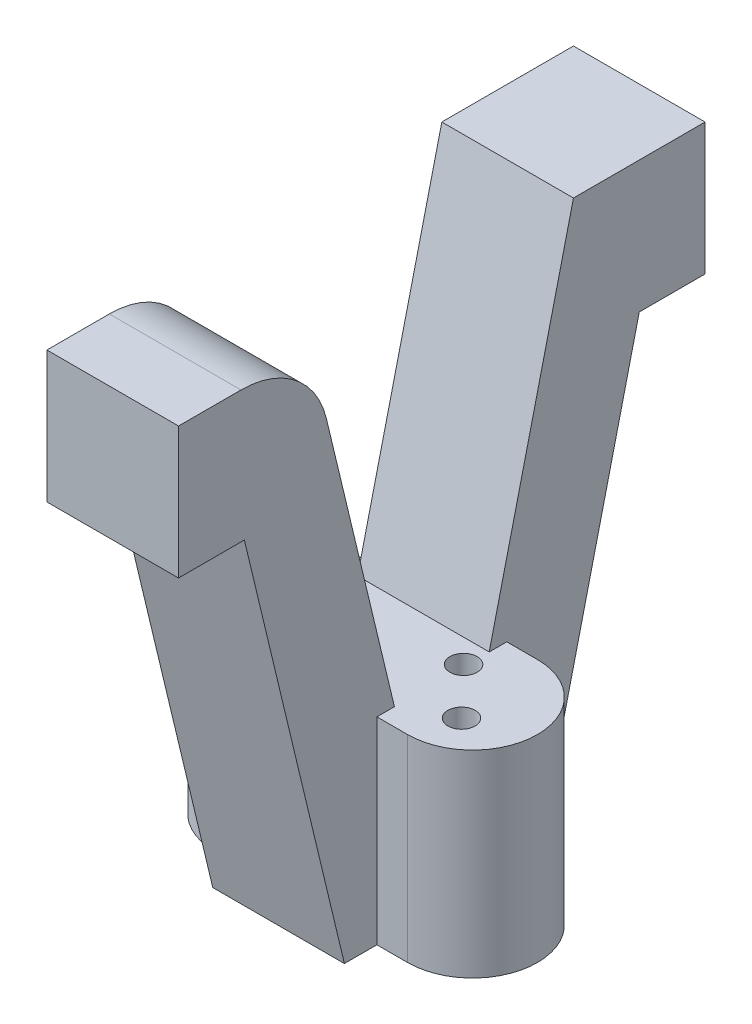
SolidWorks part; units mm, degrees
ref_plane "Front Plane" through (0, 0, 0) normal (0, 0, 1) x (1, 0, 0)
ref_plane "Top Plane" through (0, 0, 0) normal (0, 1, 0) x (1, 0, 0)
ref_plane "Right Plane" through (0, 0, 0) normal (1, 0, 0) x (0, 0, -1)
sketch "Sketch2" plane through (0, 0, 0) normal (1, 0, 0) x (0, 0, -1)
  line L0 (-6, 12.5) -> (-6, 9.5)
  line L1 (-6, 12.5) -> (0, 12.5) construction
  line L2 (-6, 9.5) -> (-4.5, 9.5)
  line L3 (-6, 12.5) -> (-3, 12.5)
  line L4 (-3, 12.5) -> (0, 0)
  line L5 (0, 0) -> (-2.22, 0)
  line L6 (-2.22, 0) -> (-4.5, 9.5)
  dimension "D1" = 6
  dimension "D2" = 3
  dimension "D3" = 1.5
  dimension "D4" = 3
  dimension "D5" = 12.5
extrude "Boss-Extrude2" add sketch "Sketch2" along normal blind 1.5 and the other way blind 1.5
fillet "Fillet1" radius 2 1 edges at (0, 12.5, 3)
sketch "Sketch1" plane through (0, 0, 0) normal (0, 1, 0) x (1, 0, 0)
  line L0 (-2.2, 0) -> (2.2, 0) construction
  line L1 (-2.2, 0) -> (2.2, 0) construction
  line L2 (-2.2, 1.48) -> (2.2, 1.48)
  line L3 (-2.2, -1.48) -> (2.2, -1.48)
  line L4 (0, 0) -> (0, -6) construction
  line L5 (1.4535, 0.542) -> (2.4904, -0.542) construction
  line L6 (1.972, 0) -> (-1.2108, 0) construction
  line L7 (1.972, 0) -> (2.9114, 0.8986) construction
  line L8 (1.972, 0) -> (0.3099, -1.5898) construction
  line L9 (-1.2108, 0) -> (0.3099, -1.5898) construction
  line L10 (-1.5, 0) -> (-1.5, -2.632) construction
  circle A0 centre (-2.2, 0) radius 0.63 construction
  circle A1 centre (2.2, 0) radius 0.63 construction
  arc A2 (-2.2, 1.48) -> (-2.2, -1.48) centre (-2.2, 0) ccw
  arc A3 (2.2, -1.48) -> (2.2, 1.48) centre (2.2, 0) ccw
  circle A4 centre (-1.2108, 0) radius 0.63
  circle A5 centre (1.4535, 0.542) radius 0.3104
  circle A6 centre (2.4904, -0.542) radius 0.3104
  point P4 (0, 0)
  point P7 (0, 0)
  point P20 (-1.841, 0)
  point P21 (0, 0)
  point P24 (-1.5, -0.6891)
  point P27 (1.424, 0.3897)
  point P28 (1.6795, 0.8818)
  point P29 (1.9756, 0)
  point P30 (3.3924, 0.7115)
  dimension "D2" = 1.26
  dimension "D3" = 1.48
  dimension "D1" = 4.4
  dimension "D4" = 6
  dimension "D6" = 1.5
  dimension "D5" = 1.8099
  dimension "D7" = 3.6
  dimension "D8" = 1.3
  dimension "D9" = 2.2
extrude "Boss-Extrude3" add sketch "Sketch1" along normal blind 4.5 contours L3 A3 L2 A2
mirror "Mirror1" about plane through (0, 0, 0) normal (0, 0, 1) of "Boss-Extrude2"
extrude "Cut-Extrude2" cut sketch "Sketch1<3>" along normal through all contours A4 | A5 | A6 region at (-1.2108, 0, 0)
sketch "Sketch1<3>" plane through (0, 0, 0) normal (0, 1, 0) x (1, 0, 0) same geometry as "Sketch1"
equation "\"TubingOD\"= 1.26"
equation "\"ConcentricDepth\"= 4.5mm"
equation "\"D2@Sketch1\"=\"TubingOD\""
equation "\"D1@Boss-Extrude3\"=\"ConcentricDepth\""
